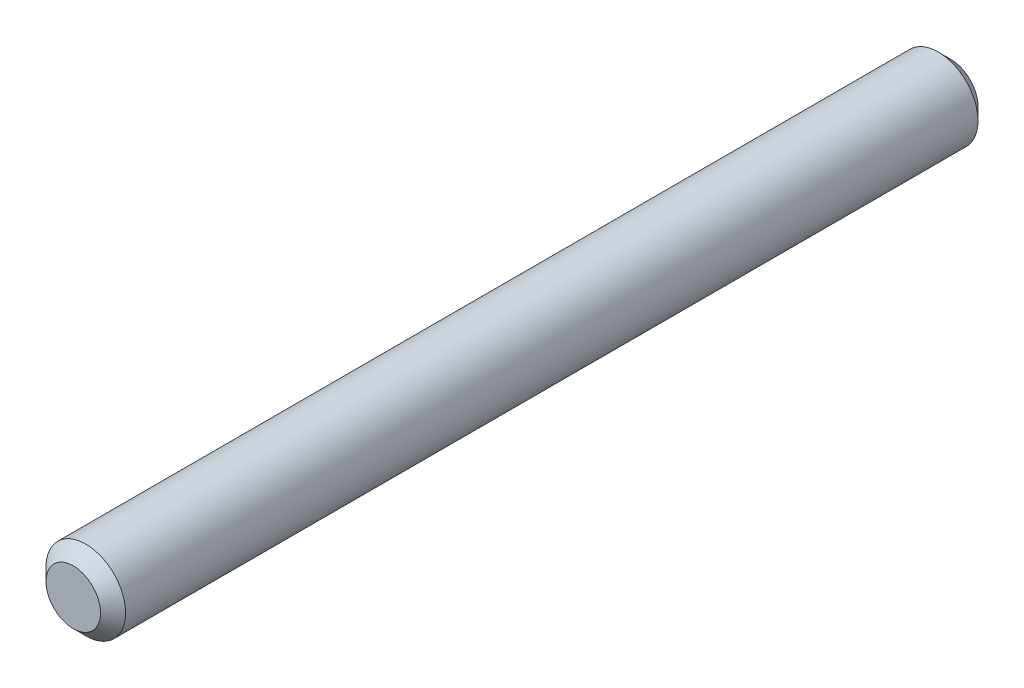
SolidWorks part; units mm, degrees
material "AISI 1020"
ref_plane "Front Plane" through (0, 0, 0) normal (0, 0, 1) x (1, 0, 0)
ref_plane "Top Plane" through (0, 0, 0) normal (0, 1, 0) x (1, 0, 0)
ref_plane "Right Plane" through (0, 0, 0) normal (1, 0, 0) x (0, 0, -1)
sketch "Sketch1" plane through (0, 0, 0) normal (0, 0, 1) x (1, 0, 0)
  circle A0 centre (0, 0) radius 3.175
  dimension "D1" = 6.35
extrude "Boss-Extrude1" add sketch "Sketch1" against normal blind 70
cosmetic thread "Cosmetic Thread1" parameters "D2"=5.268
chamfer "Chamfer1" distance 1 angle 45 2 edges at (3.175, 0, -70) (3.175, 0, 0)
